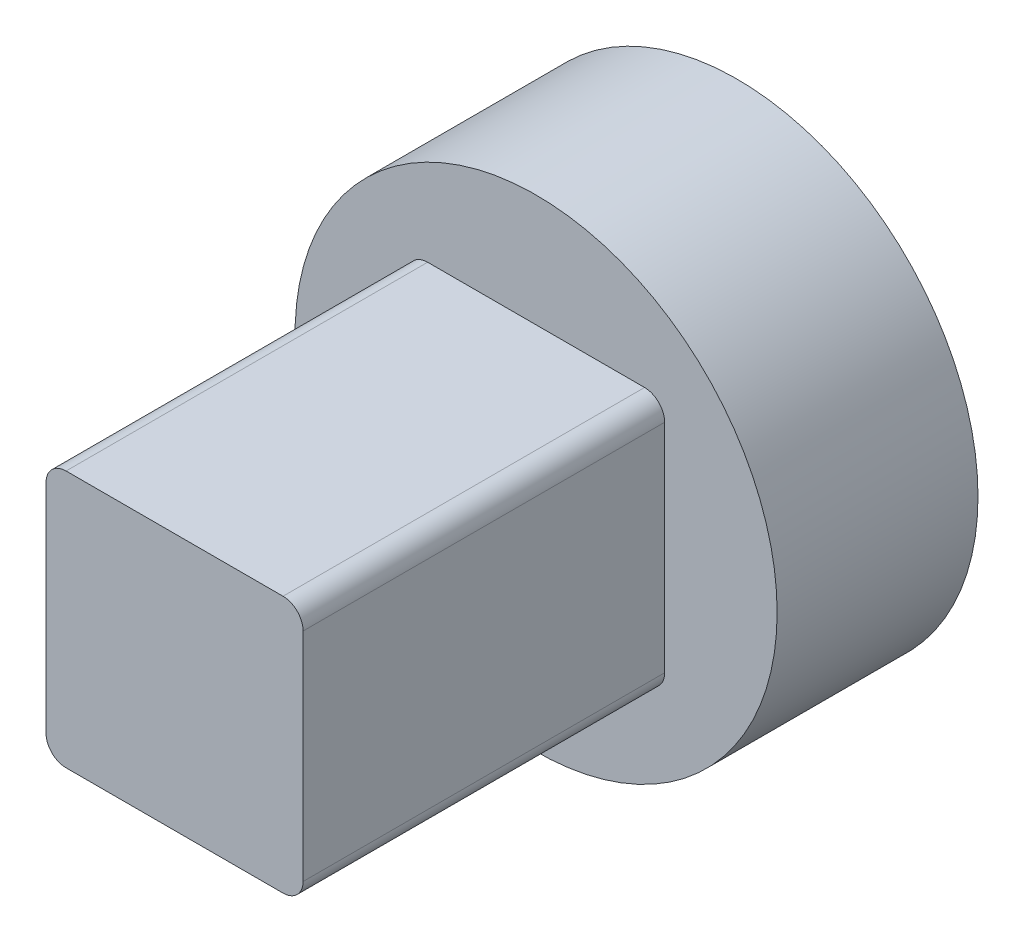
SolidWorks part; units mm, degrees
ref_plane "Front Plane" through (0, 0, 0) normal (0, 0, 1) x (1, 0, 0)
ref_plane "Top Plane" through (0, 0, 0) normal (0, 1, 0) x (1, 0, 0)
ref_plane "Right Plane" through (0, 0, 0) normal (1, 0, 0) x (0, 0, -1)
sketch "Sketch1" plane through (0, 0, -23.4655) normal (0, 0, 1) x (1, 0, 0)
  circle A0 centre (3.7405, -31.8284) radius 2.4
  circle A1 centre (3.7405, -31.8284) radius 6
  dimension "D1" = 4.8
  dimension "D2" = 12
extrude "Boss-Extrude1" add sketch "Sketch1" along normal blind 5
sketch "Sketch2" plane through (0, 0, -18.4655) normal (0, 0, 1) x (1, 0, 0)
  line L4 (3.7405, -31.8284) -> (6.9405, -31.8284) construction
  line L5 (6.9405, -31.8284) -> (6.9405, -28.6284) construction
  line L7 (6.4405, -28.6284) -> (1.0405, -28.6284)
  line L8 (6.9405, -29.1284) -> (6.9405, -34.5284)
  line L9 (6.4405, -35.0284) -> (1.0405, -35.0284)
  line L10 (0.5405, -29.1284) -> (0.5405, -34.5284)
  arc A1 (0.5405, -29.1284) -> (1.0405, -28.6284) centre (1.0405, -29.1284) cw
  arc A2 (1.0405, -35.0284) -> (0.5405, -34.5284) centre (1.0405, -34.5284) cw
  arc A3 (6.4405, -35.0284) -> (6.9405, -34.5284) centre (6.4405, -34.5284) ccw
  arc A4 (6.4405, -28.6284) -> (6.9405, -29.1284) centre (6.4405, -29.1284) cw
  point P6 (0.5405, -28.6284)
  point P12 (0.5405, -35.0284)
  point P15 (6.9405, -35.0284)
  dimension "D5" = 0.5
  dimension "D6" = 0.5
  dimension "D1" = 3.2
  dimension "D2" = 3.2
  dimension "D3" = 6.4
  dimension "D4" = 6.4
extrude "Boss-Extrude2" add sketch "Sketch2" along normal blind 9
